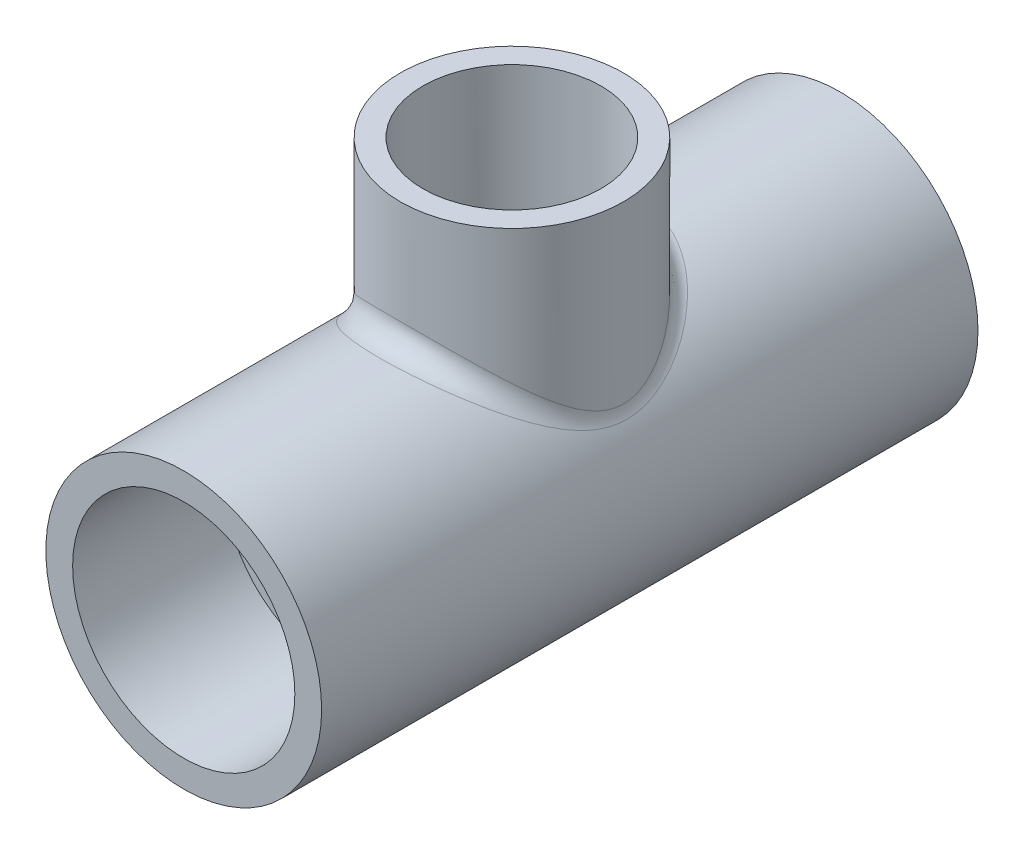
SolidWorks part; units mm, degrees
ref_plane "Front Plane" through (0, 0, 0) normal (0, 0, 1) x (1, 0, 0)
ref_plane "Top Plane" through (0, 0, 0) normal (0, 1, 0) x (1, 0, 0)
ref_plane "Right Plane" through (0, 0, 0) normal (1, 0, 0) x (0, 0, -1)
sketch "Sketch1" plane through (0, 0, 0) normal (0, 0, 1) x (1, 0, 0)
  circle A0 centre (0, 0) radius 412
  circle A1 centre (0, 0) radius 529
  circle A2 centre (0, 0) radius 656.5
  dimension "D1" = 824
  dimension "D2" = 1058
  dimension "D3" = 1313
extrude "Boss-Extrude1" add sketch "Sketch1" along normal mid plane 1685 contours A1 A0 region at (-514.0376, 0, 0)
extrude "Boss-Extrude2" add sketch "Sketch1<3>" along normal mid plane 3125 contours A2 A1 region at (-637.9314, 0, 0)
sketch "Sketch1<3>" plane through (0, 0, 0) normal (0, 0, 1) x (1, 0, 0) same geometry as "Sketch1"
ref_plane "Plane1" through (0, 1250, 0) normal (0, 1, 0) x (1, 0, 0)
sketch "Sketch2" plane through (0, 1250, 0) normal (0, 1, 0) x (1, 0, 0)
  circle A0 centre (0, 0) radius 311
  circle A1 centre (0, 0) radius 424
  circle A2 centre (0, 0) radius 531.5
  dimension "D1" = 622
  dimension "D2" = 848
  dimension "D3" = 1063
extrude "Cut-Extrude2" cut sketch "Sketch2" against normal up to next contours A0 region at (0, 1250, 0)
extrude "Cut-Extrude3" cut sketch "Sketch2<4>" against normal blind 690 contours A1 A0 region at (-412.0075, 1250, 0)
sketch "Sketch2<4>" plane through (0, 1250, 0) normal (0, 1, 0) x (1, 0, 0) same geometry as "Sketch2"
extrude "Boss-Extrude3" add sketch "Sketch2<5>" against normal up to next contours A2 A1 region at (-516.4669, 1250, 0)
sketch "Sketch2<5>" plane through (0, 1250, 0) normal (0, 1, 0) x (1, 0, 0) same geometry as "Sketch2"
fillet "Fillet1" radius 100 1 edges at (-51.7907, 654.454, -528.9707)
